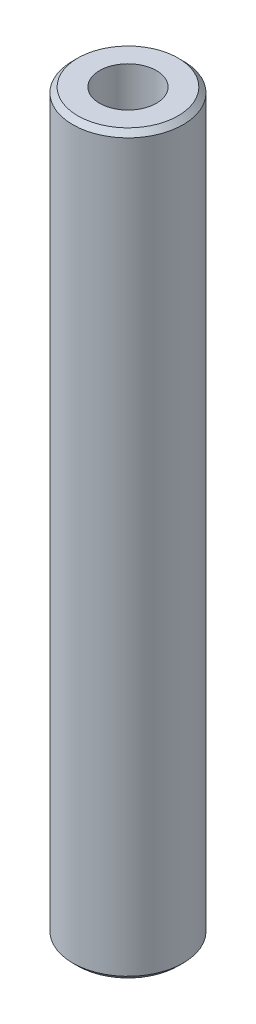
SolidWorks part; units mm, degrees
ref_plane "Front Plane" through (0, 0, 0) normal (0, 0, 1) x (1, 0, 0)
ref_plane "Top Plane" through (0, 0, 0) normal (0, 1, 0) x (1, 0, 0)
ref_plane "Right Plane" through (0, 0, 0) normal (1, 0, 0) x (0, 0, -1)
sketch "Sketch1" plane through (0, 0, 0) normal (0, 1, 0) x (1, 0, 0)
  circle A0 centre (0, 0) radius 45
  dimension "SHAFT_OD" = 90
extrude "Boss-Extrude1" add sketch "Sketch1" along normal blind 600
sketch "Sketch2" plane through (0, 0, 0) normal (0, 1, 0) x (1, 0, 0)
  circle A0 centre (0, 0) radius 23.1411
  dimension "BORE_D" = 46.2822
extrude "Cut-Extrude1" cut sketch "Sketch2" along normal through all
chamfer "Chamfer1" distance 4.1508 angle 45 2 edges at (0, 600, 45) (0, 0, 45)
